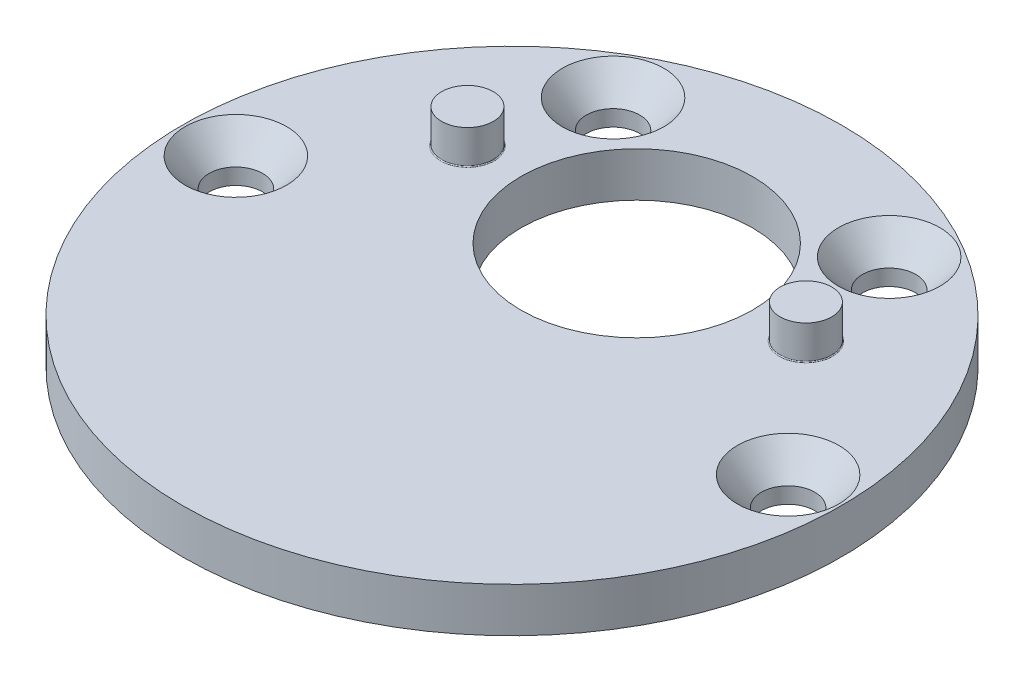
SolidWorks part; units mm, degrees
ref_plane "Front Plane" through (0, 0, 0) normal (0, 0, 1) x (1, 0, 0)
ref_plane "Top Plane" through (0, 0, 0) normal (0, 1, 0) x (1, 0, 0)
ref_plane "Right Plane" through (0, 0, 0) normal (1, 0, 0) x (0, 0, -1)
sketch "Sketch1" plane through (0, 0, 0) normal (0, 1, 0) x (1, 0, 0)
  line L4 (0, 0) -> (15.8817, 0) construction
  line L5 (0, 0) -> (0, 17.0912) construction
  line L6 (-7.75, 13.4234) -> (0, 0) construction
  line L7 (0, 0) -> (7.75, 13.4234) construction
  circle A0 centre (0, 0) radius 15.5 construction
  circle A1 centre (-7.75, 13.4234) radius 1.5
  circle A3 centre (-15.5, 0) radius 1.5
  circle A4 centre (7.75, 13.4234) radius 1.5
  circle A5 centre (15.5, 0) radius 1.5
  circle A6 centre (0, 0) radius 18.5
  dimension "D1" = 31
  dimension "D2" = 3
  dimension "D4" = 37
  dimension "D3" = 60
extrude "Boss-Extrude1" add sketch "Sketch1" along normal blind 2.5
sketch "Sketch2" plane through (0, 2.5, 0) normal (0, 1, 0) x (1, 0, 0)
  line L0 (0, 0) -> (0, 16.6144) construction
  line L1 (0, 0) -> (25.2906, 0) construction
  line L2 (-9.5, 7) -> (9.5, 7) construction
  circle A0 centre (-9.5, 7) radius 1.45
  circle A1 centre (9.5, 7) radius 1.45
  point P8 (0, 8.3072)
  point P11 (0, 7)
  dimension "D3" = 2.9
  dimension "D1" = 7
  dimension "D2" = 19
extrude "Boss-Extrude2" add sketch "Sketch2" along normal blind 1.9
fillet "Fillet1" radius 0.05 2 edges at (9.5, 2.5, -5.55) (-9.5, 2.5, -5.55)
sketch "Sketch4" plane through (0, 2.5, 0) normal (0, 1, 0) x (1, 0, 0)
  line L0 (9.5, 7) -> (-9.5, 7) construction
  circle A0 centre (0, 7) radius 6.5
  dimension "D1" = 13
extrude "Cut-Extrude1" cut sketch "Sketch4" against normal through all
chamfer "Chamfer1" distance 1.35 distance2 1.6 4 edges at (-15.5, 2.5, 1.5) (15.5, 2.5, 1.5) (7.75, 2.5, -11.9234) (-7.75, 2.5, -11.9234) first distance on face at (0, 2.5, -0.5)
